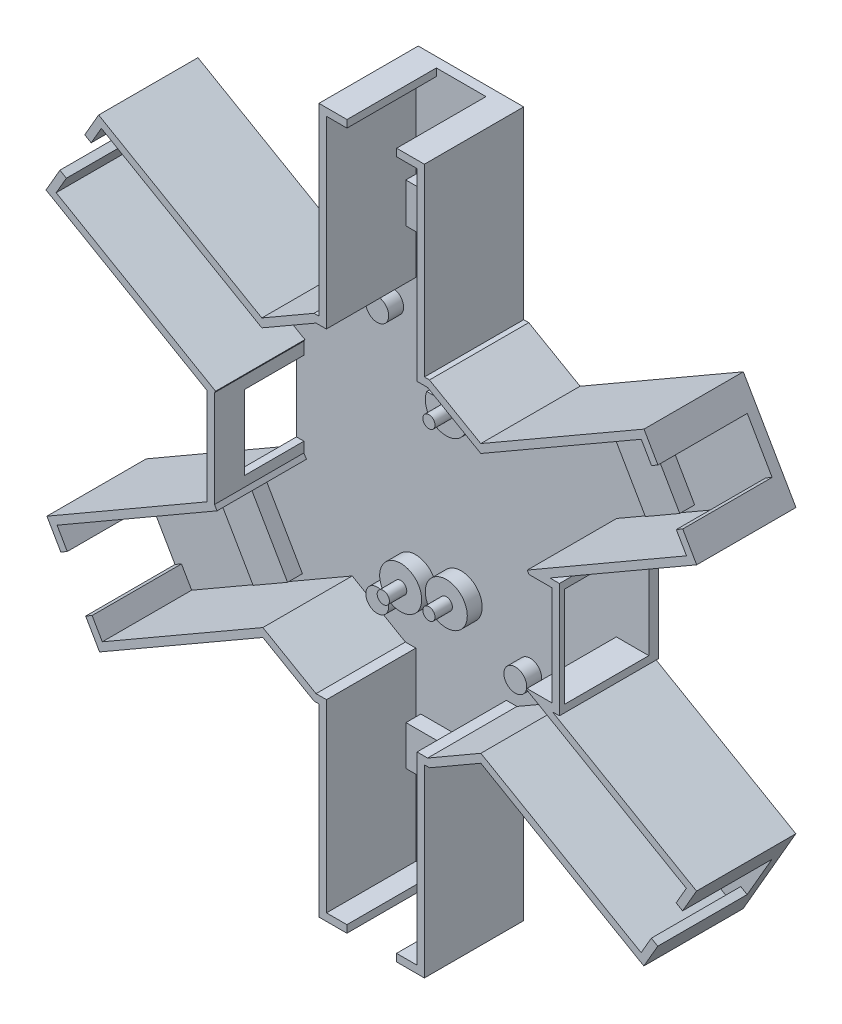
SolidWorks part; units mm, degrees
ref_plane "Ebene vorne" through (0, 0, 0) normal (0, 0, 1) x (1, 0, 0)
ref_plane "Ebene oben" through (0, 0, 0) normal (0, 1, 0) x (1, 0, 0)
ref_plane "Ebene rechts" through (0, 0, 0) normal (1, 0, 0) x (0, 0, -1)
sketch "Skizze1" plane through (0, 0, 0) normal (0, 0, 1) x (1, 0, 0)
  line L0 (-22.15, 25.11) -> (-11.02, 31.53) construction
  line L1 (-11.02, 31.53) -> (-8.35, 31.53) construction
  line L2 (-8.35, 31.53) -> (-8.35, 68.65) construction
  line L3 (-8.35, 68.65) -> (8.29, 68.65) construction
  line L4 (8.29, 68.65) -> (8.29, 31.53) construction
  line L5 (8.29, 31.53) -> (11, 31.53) construction
  line L6 (11, 31.53) -> (21.95, 25.25) construction
  line L7 (21.95, 25.25) -> (53.98, 43.72) construction
  line L8 (53.98, 43.72) -> (62.29, 29.33) construction
  line L9 (-62.48, 29.19) -> (-54.18, 43.59) construction
  line L10 (-54.18, 43.59) -> (-22.15, 25.11) construction
  line L11 (-30.38, 10.62) -> (-62.48, 29.19) construction
  line L12 (-30.88, 9.75) -> (-30.38, 10.62) construction
  line L13 (-30.88, -9.32) -> (-30.88, 9.75) construction
  line L14 (-30.05, -10.67) -> (-30.88, -9.32) construction
  line L15 (-62.3, -29.3) -> (-30.05, -10.67) construction
  line L16 (-53.99, -43.7) -> (-62.3, -29.3) construction
  line L17 (-21.73, -25.09) -> (-53.99, -43.7) construction
  line L18 (-21.52, -25.46) -> (-21.73, -25.09) construction
  line L19 (-11.02, -31.51) -> (-21.52, -25.46) construction
  line L20 (-8.33, -31.51) -> (-11.02, -31.51) construction
  line L21 (-8.33, -68.7) -> (-8.33, -31.51) construction
  line L22 (8.29, -68.7) -> (-8.33, -68.7) construction
  line L23 (8.31, -31.51) -> (8.29, -68.7) construction
  line L24 (11.02, -31.51) -> (8.31, -31.51) construction
  line L25 (21.5, -25.46) -> (11.02, -31.51) construction
  line L26 (21.73, -25.06) -> (21.5, -25.46) construction
  line L27 (53.95, -43.66) -> (21.73, -25.06) construction
  line L28 (62.26, -29.27) -> (53.95, -43.66) construction
  line L29 (30.04, -10.67) -> (62.26, -29.27) construction
  line L30 (30.79, -9.37) -> (30.04, -10.67) construction
  line L31 (35.49, -9.37) -> (30.79, -9.37) construction
  line L32 (35.49, 9.12) -> (35.49, -9.37) construction
  line L33 (31.19, 9.12) -> (35.49, 9.12) construction
  line L34 (30.22, 10.81) -> (31.19, 9.12) construction
  line L35 (62.29, 29.33) -> (30.22, 10.81) construction
  line L36 (-22.15, 25.11) -> (-11.02, 31.53) construction
  line L37 (-11.02, 31.53) -> (-8.35, 31.53) construction
  line L38 (-8.35, 31.53) -> (-8.35, 68.65) construction
  line L39 (-8.35, 68.65) -> (8.29, 68.65) construction
  line L40 (8.29, 68.65) -> (8.29, 31.53) construction
  line L41 (8.29, 31.53) -> (11, 31.53) construction
  line L42 (11, 31.53) -> (21.95, 25.25) construction
  line L43 (21.95, 25.25) -> (53.98, 43.72) construction
  line L44 (53.98, 43.72) -> (62.29, 29.33) construction
  line L45 (-62.48, 29.19) -> (-54.18, 43.59) construction
  line L46 (-54.18, 43.59) -> (-22.15, 25.11) construction
  line L47 (-30.38, 10.62) -> (-62.48, 29.19) construction
  line L48 (-30.88, 9.75) -> (-30.38, 10.62) construction
  line L49 (-30.88, -9.32) -> (-30.88, 9.75) construction
  line L50 (-30.05, -10.67) -> (-30.88, -9.32) construction
  line L51 (-62.3, -29.3) -> (-30.05, -10.67) construction
  line L52 (-53.99, -43.7) -> (-62.3, -29.3) construction
  line L53 (-21.73, -25.09) -> (-53.99, -43.7) construction
  line L54 (-21.52, -25.46) -> (-21.73, -25.09) construction
  line L55 (-11.02, -31.51) -> (-21.52, -25.46) construction
  line L56 (-8.33, -31.51) -> (-11.02, -31.51) construction
  line L57 (-8.33, -68.7) -> (-8.33, -31.51) construction
  line L58 (8.29, -68.7) -> (-8.33, -68.7) construction
  line L59 (8.31, -31.51) -> (8.29, -68.7) construction
  line L60 (11.02, -31.51) -> (8.31, -31.51) construction
  line L61 (21.5, -25.46) -> (11.02, -31.51) construction
  line L62 (21.73, -25.06) -> (21.5, -25.46) construction
  line L63 (53.95, -43.66) -> (21.73, -25.06) construction
  line L64 (62.26, -29.27) -> (53.95, -43.66) construction
  line L65 (30.04, -10.67) -> (62.26, -29.27) construction
  line L66 (30.79, -9.37) -> (30.04, -10.67) construction
  line L67 (35.49, -9.37) -> (30.79, -9.37) construction
  line L68 (35.49, 9.12) -> (35.49, -9.37) construction
  line L69 (31.19, 9.12) -> (35.49, 9.12) construction
  line L70 (30.22, 10.81) -> (31.19, 9.12) construction
  line L71 (62.29, 29.33) -> (30.22, 10.81) construction
  line L72 (-22.15, 26.0336) -> (-11.2342, 32.33)
  line L73 (-11.2342, 32.33) -> (-9.15, 32.33)
  line L74 (-9.15, 32.33) -> (-9.15, 69.45)
  line L75 (-9.15, 69.45) -> (9.09, 69.45)
  line L76 (9.09, 69.45) -> (9.09, 32.33)
  line L77 (9.09, 32.33) -> (11.2131, 32.33)
  line L78 (11.2131, 32.33) -> (21.9489, 26.1729)
  line L79 (21.9489, 26.1729) -> (54.273, 44.8124)
  line L80 (54.273, 44.8124) -> (63.3828, 29.0373)
  line L81 (63.3828, 29.0373) -> (31.311, 10.5162)
  line L82 (31.311, 10.5162) -> (31.6532, 9.92)
  line L83 (31.6532, 9.92) -> (36.29, 9.92)
  line L84 (36.29, 9.92) -> (36.29, -10.17)
  line L85 (36.29, -10.17) -> (31.2521, -10.17)
  line L86 (31.2521, -10.17) -> (31.1326, -10.377)
  line L87 (31.1326, -10.377) -> (63.3529, -28.9772)
  line L88 (63.3529, -28.9772) -> (54.2428, -44.7527)
  line L89 (54.2428, -44.7527) -> (21.9615, -26.1173)
  line L90 (21.9615, -26.1173) -> (21.9615, -26.1173)
  line L91 (21.9615, -26.1173) -> (11.2343, -32.31)
  line L92 (11.2343, -32.31) -> (9.1096, -32.31)
  line L93 (9.1096, -32.31) -> (9.0896, -69.5)
  line L94 (9.0896, -69.5) -> (-9.13, -69.5)
  line L95 (-9.13, -69.5) -> (-9.13, -32.31)
  line L96 (-9.13, -32.31) -> (-11.234, -32.31)
  line L97 (-11.234, -32.31) -> (-21.9457, -26.138)
  line L98 (-21.9457, -26.138) -> (-21.9457, -26.138)
  line L99 (-21.9457, -26.138) -> (-54.2831, -44.7927)
  line L100 (-54.2831, -44.7927) -> (-63.3926, -29.0073)
  line L101 (-63.3926, -29.0073) -> (-31.1621, -10.3886)
  line L102 (-31.1621, -10.3886) -> (-31.68, -9.5463)
  line L103 (-31.68, -9.5463) -> (-31.68, 9.9635)
  line L104 (-31.68, 9.9635) -> (-31.4711, 10.327)
  line L105 (-31.4711, 10.327) -> (-63.572, 28.8975)
  line L106 (-63.572, 28.8975) -> (-54.4734, 44.6829)
  line L107 (-54.4734, 44.6829) -> (-22.15, 26.0336)
  line L108 (-22.1499, 27.7653) -> (-11.6358, 33.83)
  line L109 (-11.6358, 33.83) -> (-10.65, 33.83)
  line L110 (-10.65, 33.83) -> (-10.65, 70.95)
  line L111 (-10.65, 70.95) -> (10.59, 70.95)
  line L112 (10.59, 70.95) -> (10.59, 33.83)
  line L113 (10.59, 33.83) -> (11.6127, 33.83)
  line L114 (11.6127, 33.83) -> (21.9469, 27.9032)
  line L115 (21.9469, 27.9032) -> (54.8223, 46.8607)
  line L116 (54.8223, 46.8607) -> (65.4319, 28.4885)
  line L117 (65.4319, 28.4885) -> (35.8755, 11.42)
  line L118 (35.8755, 11.42) -> (35.8755, 11.42)
  line L119 (35.8755, 11.42) -> (37.79, 11.42)
  line L120 (37.79, 11.42) -> (37.79, -11.67)
  line L121 (37.79, -11.67) -> (36.3727, -11.67)
  line L122 (36.3727, -11.67) -> (36.3727, -11.67)
  line L123 (36.3727, -11.67) -> (65.4021, -28.4282)
  line L124 (65.4021, -28.4282) -> (54.7917, -46.8016)
  line L125 (54.7917, -46.8016) -> (21.9615, -27.8493)
  line L126 (21.9615, -27.8493) -> (21.9615, -27.8493)
  line L127 (21.9615, -27.8493) -> (11.6362, -33.81)
  line L128 (11.6362, -33.81) -> (10.6088, -33.81)
  line L129 (10.6088, -33.81) -> (10.5888, -71)
  line L130 (10.5888, -71) -> (-10.63, -71)
  line L131 (-10.63, -71) -> (-10.63, -33.81)
  line L132 (-10.63, -33.81) -> (-11.6352, -33.81)
  line L133 (-11.6352, -33.81) -> (-21.9453, -27.8694)
  line L134 (-21.9453, -27.8694) -> (-21.9453, -27.8694)
  line L135 (-21.9453, -27.8694) -> (-54.8327, -46.8414)
  line L136 (-54.8327, -46.8414) -> (-65.4412, -28.4584)
  line L137 (-65.4412, -28.4584) -> (-33.18, -9.8219)
  line L138 (-33.18, -9.8219) -> (-33.18, -9.8219)
  line L139 (-33.18, -9.8219) -> (-33.18, 9.5827)
  line L140 (-33.18, 9.5827) -> (-33.18, 9.5827)
  line L141 (-33.18, 9.5827) -> (-65.6194, 28.349)
  line L142 (-65.6194, 28.349) -> (-55.0236, 46.7321)
  line L143 (-55.0236, 46.7321) -> (-22.1499, 27.7653)
  dimension "D1" = 0.8
  dimension "D2" = 1.5
extrude "Aufsatz-Linear austragen1" add sketch "Skizze1" along normal blind 18
sketch "Skizze3" plane through (0, 0, 0) normal (0, 0, -1) x (-1, 0, 0)
  line L31 (55.0236, 46.7321) -> (22.1499, 27.7653)
  line L32 (22.1499, 27.7653) -> (11.6358, 33.83)
  line L33 (11.6358, 33.83) -> (10.65, 33.83)
  line L34 (10.65, 33.83) -> (10.65, 70.95)
  line L35 (10.65, 70.95) -> (-10.59, 70.95)
  line L36 (-10.59, 70.95) -> (-10.59, 33.83)
  line L37 (-10.59, 33.83) -> (-11.6127, 33.83)
  line L38 (-11.6127, 33.83) -> (-21.9469, 27.9032)
  line L39 (-21.9469, 27.9032) -> (-54.8223, 46.8607)
  line L40 (-54.8223, 46.8607) -> (-65.4319, 28.4885)
  line L41 (-65.4319, 28.4885) -> (-35.8755, 11.42)
  line L42 (-35.8755, 11.42) -> (-37.79, 11.42)
  line L43 (-37.79, 11.42) -> (-37.79, -11.67)
  line L44 (-37.79, -11.67) -> (-36.3727, -11.67)
  line L45 (-36.3727, -11.67) -> (-65.4021, -28.4282)
  line L46 (-65.4021, -28.4282) -> (-54.7917, -46.8016)
  line L47 (-54.7917, -46.8016) -> (-21.9615, -27.8493)
  line L48 (-21.9615, -27.8493) -> (-11.6362, -33.81)
  line L49 (-11.6362, -33.81) -> (-10.6088, -33.81)
  line L50 (-10.6088, -33.81) -> (-10.5888, -71)
  line L51 (-10.5888, -71) -> (10.63, -71)
  line L52 (10.63, -71) -> (10.63, -33.81)
  line L53 (10.63, -33.81) -> (11.6352, -33.81)
  line L54 (11.6352, -33.81) -> (21.9453, -27.8694)
  line L55 (21.9453, -27.8694) -> (54.8327, -46.8414)
  line L56 (54.8327, -46.8414) -> (65.4412, -28.4584)
  line L57 (65.4412, -28.4584) -> (33.18, -9.8219)
  line L59 (33.18, -9.8219) -> (33.18, 9.5827)
  line L60 (33.18, 9.5827) -> (65.6194, 28.349)
  line L61 (65.6194, 28.349) -> (55.0236, 46.7321)
  line L62 (55.0236, 46.7321) -> (22.1499, 27.7653)
  line L63 (22.1499, 27.7653) -> (11.6358, 33.83)
  line L64 (11.6358, 33.83) -> (10.65, 33.83)
  line L65 (10.65, 33.83) -> (10.65, 70.95)
  line L66 (10.65, 70.95) -> (-10.59, 70.95)
  line L67 (-10.59, 70.95) -> (-10.59, 33.83)
  line L68 (-10.59, 33.83) -> (-11.6127, 33.83)
  line L69 (-11.6127, 33.83) -> (-21.9469, 27.9032)
  line L70 (-21.9469, 27.9032) -> (-54.8223, 46.8607)
  line L71 (-54.8223, 46.8607) -> (-65.4319, 28.4885)
  line L72 (-65.4319, 28.4885) -> (-35.8755, 11.42)
  line L73 (-35.8755, 11.42) -> (-37.79, 11.42)
  line L74 (-37.79, 11.42) -> (-37.79, -11.67)
  line L75 (-37.79, -11.67) -> (-36.3727, -11.67)
  line L76 (-36.3727, -11.67) -> (-65.4021, -28.4282)
  line L77 (-65.4021, -28.4282) -> (-54.7917, -46.8016)
  line L78 (-54.7917, -46.8016) -> (-21.9615, -27.8493)
  line L79 (-21.9615, -27.8493) -> (-11.6362, -33.81)
  line L80 (-11.6362, -33.81) -> (-10.6088, -33.81)
  line L81 (-10.6088, -33.81) -> (-10.5888, -71)
  line L82 (-10.5888, -71) -> (10.63, -71)
  line L83 (10.63, -71) -> (10.63, -33.81)
  line L84 (10.63, -33.81) -> (11.6352, -33.81)
  line L85 (11.6352, -33.81) -> (21.9453, -27.8694)
  line L86 (21.9453, -27.8694) -> (54.8327, -46.8414)
  line L87 (54.8327, -46.8414) -> (65.4412, -28.4584)
  line L88 (65.4412, -28.4584) -> (33.18, -9.8219)
  line L90 (33.18, -9.8219) -> (33.18, 9.5827)
  line L91 (33.18, 9.5827) -> (65.6194, 28.349)
  line L92 (65.6194, 28.349) -> (55.0236, 46.7321)
  dimension "D1" = 0
extrude "Aufsatz-Linear austragen2" add sketch "Skizze3" along normal blind 2
sketch "Skizze4" plane through (36.29, 0, 0) normal (-1, 0, 0) x (0, 0, 1)
  line L0 (17.0038, 9.92) -> (17.0038, -10.17)
  line L1 (0.8513, 9.92) -> (0, 9.92)
  line L2 (17.0038, -10.17) -> (0.8513, -10.17)
  line L3 (17.0038, 9.92) -> (0.8513, 9.92)
  line L4 (0, 9.92) -> (0, -10.17)
  line L5 (0, -10.17) -> (18, -10.17)
  line L6 (18, -10.17) -> (18, 9.92)
  line L7 (18, 9.92) -> (0, 9.92)
  line L8 (0, 9.92) -> (0, -10.17) construction
  line L9 (0, -10.17) -> (18, -10.17) construction
  line L10 (18, -10.17) -> (18, 9.92) construction
  line L11 (18, 9.92) -> (0, 9.92) construction
  line L12 (0, 9.92) -> (0, -10.17)
  line L13 (0, -10.17) -> (0.8513, -10.17)
  dimension "D1" = 0
extrude "Schnitt-Linear austragen1" cut sketch "Skizze4" against normal up to next
sketch "Skizze5" plane through (-31.68, 0, 0) normal (1, 0, 0) x (0, 0, -1)
  line L0 (-12, -7.5) -> (-12, 7.5)
  line L1 (-12, -7.5) -> (0, -7.5)
  line L2 (-12, 7.5) -> (0, 7.5)
  line L3 (0, -7.5) -> (0, 7.5)
  line L4 (-12, -7.5) -> (0, 7.5) construction
  line L5 (-12, 7.5) -> (0, -7.5) construction
  line L6 (0, 9.9635) -> (0, -9.5463) construction
  point P1 (-6, 0)
  dimension "D1" = 15
  dimension "D2" = 12
  dimension "D3" = 0
extrude "Schnitt-Linear austragen2" cut sketch "Skizze5" against normal up to next
sketch "Skizze6" plane through (0, -71, 0) normal (0, -1, 0) x (1, 0, 0)
  line L0 (-9.13, 0) -> (9.0896, 0) construction
  line L1 (5, 10) -> (-5, 10)
  line L2 (5, 10) -> (5, 0)
  line L3 (5, 0) -> (-5, 0)
  line L4 (-5, 10) -> (-5, 0)
  line L5 (5, 10) -> (-5, 0) construction
  line L6 (5, 0) -> (-5, 10) construction
  line L7 (-9.13, 0) -> (9.0896, 0) construction
  point P0 (0, 5)
  dimension "D1" = 10
  dimension "D2" = 10
sketch "Skizze7" plane through (0, 0, 0) normal (0, 0, 1) x (1, 0, 0)
  circle A0 centre (-9.19, -20.27) radius 1.35 construction
  circle A1 centre (0, -18.5) radius 1.35 construction
  circle A2 centre (0, 15) radius 1.35 construction
  circle A3 centre (-9.19, -20.27) radius 4.35
  circle A4 centre (0, -18.5) radius 4.35
  circle A5 centre (0, 15) radius 4.35
  circle A6 centre (0, 15) radius 1.23
  circle A7 centre (0, -18.5) radius 1.23
  circle A8 centre (-9.19, -20.27) radius 1.23
  point P0 (-9.19, -21.62)
  point P1 (-7.84, -20.27)
  point P2 (-9.19, -18.92)
  point P3 (0, -17.15)
  point P5 (-1.35, -18.5)
  point P6 (0, -19.85)
  point P7 (-1.35, 15)
  point P8 (0, 16.35)
  point P13 (1.35, 15)
  dimension "D1" = 3
  dimension "D2" = 0.12
  dimension "D3" = 0.12
  dimension "D4" = 0.12
extrude "Aufsatz-Linear austragen3" add sketch "Skizze7" along normal blind 6.5 contours A6 | A7 | A8
sketch "Skizze8" plane through (0, 0, 0) normal (0, 0, 1) x (1, 0, 0)
  line L0 (3.9365, 16.5483) -> (-3.9365, 16.5483)
  circle A0 centre (-9.19, -20.27) radius 1.23 construction
  circle A1 centre (-9.19, -20.27) radius 1.23 construction
  circle A2 centre (0, -18.5) radius 1.23 construction
  circle A3 centre (0, -18.5) radius 1.23 construction
  circle A4 centre (0, 15) radius 1.23 construction
  circle A5 centre (0, 15) radius 1.23 construction
  circle A6 centre (-9.19, -20.27) radius 4.23
  circle A7 centre (0, -18.5) radius 4.23
  arc A8 (-3.9365, 16.5483) -> (3.9365, 16.5483) centre (0, 15) ccw
  circle A9 centre (0, 15) radius 4.23 construction
  circle A10 centre (13.9, 25.8971) radius 2.3
  circle A11 centre (-13.9, 25.8971) radius 2.3
  circle A12 centre (13.9, -24.8616) radius 2.3
  circle A13 centre (-13.9, -24.8616) radius 2.3
  dimension "D2" = 4.6
  dimension "D3" = 4.6
  dimension "D4" = 4.6
  dimension "D5" = 4.6
  dimension "D6" = 13.9
  dimension "D7" = 13.9
  dimension "D1" = 3
extrude "Aufsatz-Linear austragen4" add sketch "Skizze8" along normal blind 3
sketch "Skizze9" plane through (0, 0, 0) normal (0, 0, 1) x (1, 0, 0)
  line L0 (-9.13, -42.31) -> (-9.13, -52.31) construction
  line L1 (-9.13, -42.31) -> (9.0954, -42.31) construction
  line L2 (-9.13, -52.31) -> (9.0954, -52.31) construction
  line L3 (9.0954, -42.31) -> (9.0954, -52.31) construction
  line L4 (30.622, -31.1169) -> (39.2825, -36.1164) construction
  line L5 (30.622, -31.1169) -> (39.7347, -15.3313) construction
  line L6 (39.2825, -36.1164) -> (48.3952, -20.3309) construction
  line L7 (39.7347, -15.3313) -> (48.3952, -20.3309) construction
  line L8 (39.7303, 15.3783) -> (48.3901, 20.3792) construction
  line L9 (39.7303, 15.3783) -> (30.62, 31.1541) construction
  line L10 (48.3901, 20.3792) -> (39.2797, 36.155) construction
  line L11 (30.62, 31.1541) -> (39.2797, 36.155) construction
  line L12 (9.09, 42.33) -> (9.09, 52.33) construction
  line L13 (9.09, 42.33) -> (-9.1623, 42.33) construction
  line L14 (9.09, 52.33) -> (-9.1623, 52.33) construction
  line L15 (-9.1623, 42.33) -> (-9.1623, 52.33) construction
  line L16 (-39.4734, 36.0285) -> (-30.8117, 31.031) construction
  line L17 (-39.4734, 36.0285) -> (-48.6218, 20.1723) construction
  line L18 (-30.8117, 31.031) -> (-39.9601, 15.1748) construction
  line L19 (-48.6218, 20.1723) -> (-39.9601, 15.1748) construction
  line L20 (-48.3915, -20.3415) -> (-39.7324, -15.3394) construction
  line L21 (-48.3915, -20.3415) -> (-39.2717, -36.1285) construction
  line L22 (-39.7324, -15.3394) -> (-30.6127, -31.1264) construction
  line L23 (-39.2717, -36.1285) -> (-30.6127, -31.1264) construction
  line L24 (-39.107, 34.6626) -> (-47.2559, 20.5387)
  line L25 (-47.2559, 20.5387) -> (-40.3265, 16.5407)
  line L26 (-32.1776, 30.6646) -> (-40.3265, 16.5407)
  line L27 (-39.107, 34.6626) -> (-32.1776, 30.6646)
  line L28 (-8.1623, 43.33) -> (-8.1623, 51.33)
  line L29 (8.09, 51.33) -> (-8.1623, 51.33)
  line L30 (8.09, 43.33) -> (8.09, 51.33)
  line L31 (8.09, 43.33) -> (-8.1623, 43.33)
  line L32 (40.0962, 16.7443) -> (31.9861, 30.7882)
  line L33 (31.9861, 30.7882) -> (38.9139, 34.7889)
  line L34 (47.024, 20.745) -> (38.9139, 34.7889)
  line L35 (40.0962, 16.7443) -> (47.024, 20.745)
  line L36 (40.1008, -16.6973) -> (47.0292, -20.6969)
  line L37 (38.9164, -34.7504) -> (47.0292, -20.6969)
  line L38 (31.988, -30.7508) -> (38.9164, -34.7504)
  line L39 (31.988, -30.7508) -> (40.1008, -16.6973)
  line L40 (8.0954, -43.31) -> (8.0954, -51.31)
  line L41 (-8.13, -51.31) -> (8.0954, -51.31)
  line L42 (-8.13, -43.31) -> (-8.13, -51.31)
  line L43 (-8.13, -43.31) -> (8.0954, -43.31)
  line L44 (-38.906, -34.7624) -> (-31.9788, -30.7607)
  line L45 (-40.0981, -16.7055) -> (-31.9788, -30.7607)
  line L46 (-47.0253, -20.7072) -> (-40.0981, -16.7055)
  line L47 (-47.0253, -20.7072) -> (-38.906, -34.7624)
  line L50 (-11.2342, 32.33) -> (-22.15, 26.0336)
  line L51 (-22.15, 26.0336) -> (-54.4734, 44.6829)
  line L52 (-54.4734, 44.6829) -> (-63.572, 28.8975)
  line L53 (-63.572, 28.8975) -> (-31.4711, 10.327)
  line L54 (-31.4711, 10.327) -> (-31.68, 9.9635)
  line L55 (-31.68, 9.9635) -> (-31.68, 7.5)
  line L56 (-31.68, 7.5) -> (-33.18, 7.5)
  line L57 (-33.18, 7.5) -> (-33.18, -7.5)
  line L58 (-33.18, -7.5) -> (-31.68, -7.5)
  line L59 (-31.68, -7.5) -> (-31.68, -9.5463)
  line L60 (-31.68, -9.5463) -> (-31.1621, -10.3886)
  line L61 (-31.1621, -10.3886) -> (-63.3926, -29.0073)
  line L62 (-63.3926, -29.0073) -> (-54.2831, -44.7927)
  line L63 (-54.2831, -44.7927) -> (-21.9457, -26.138)
  line L64 (-21.9457, -26.138) -> (-11.234, -32.31)
  line L65 (-11.234, -32.31) -> (-9.13, -32.31)
  line L66 (-9.13, -32.31) -> (-9.13, -69.5)
  line L67 (-9.13, -69.5) -> (9.0896, -69.5)
  line L68 (9.0896, -69.5) -> (9.1096, -32.31)
  line L69 (9.1096, -32.31) -> (11.2343, -32.31)
  line L70 (11.2343, -32.31) -> (21.9615, -26.1173)
  line L71 (21.9615, -26.1173) -> (54.2428, -44.7527)
  line L72 (54.2428, -44.7527) -> (63.3529, -28.9772)
  line L73 (63.3529, -28.9772) -> (31.1326, -10.377)
  line L74 (31.1326, -10.377) -> (31.2521, -10.17)
  line L75 (31.2521, -10.17) -> (37.79, -10.17)
  line L76 (37.79, -10.17) -> (37.79, 9.92)
  line L77 (37.79, 9.92) -> (31.6532, 9.92)
  line L78 (31.6532, 9.92) -> (31.311, 10.5162)
  line L79 (31.311, 10.5162) -> (63.3828, 29.0373)
  line L80 (63.3828, 29.0373) -> (54.273, 44.8124)
  line L81 (54.273, 44.8124) -> (21.9489, 26.1729)
  line L82 (21.9489, 26.1729) -> (11.2131, 32.33)
  line L83 (11.2131, 32.33) -> (9.09, 32.33)
  line L84 (9.09, 32.33) -> (9.09, 69.45)
  line L85 (9.09, 69.45) -> (-9.15, 69.45)
  line L86 (-9.15, 69.45) -> (-9.15, 32.33)
  line L87 (-9.15, 32.33) -> (-11.2342, 32.33)
  line L88 (-11.2342, 32.33) -> (-22.15, 26.0336) construction
  line L89 (-22.15, 26.0336) -> (-54.4734, 44.6829) construction
  line L90 (-54.4734, 44.6829) -> (-63.572, 28.8975) construction
  line L91 (-63.572, 28.8975) -> (-31.4711, 10.327) construction
  line L92 (-31.4711, 10.327) -> (-31.68, 9.9635) construction
  line L93 (-31.68, 9.9635) -> (-31.68, 7.5) construction
  line L94 (-31.68, 7.5) -> (-33.18, 7.5) construction
  line L95 (-33.18, 7.5) -> (-33.18, -7.5) construction
  line L96 (-33.18, -7.5) -> (-31.68, -7.5) construction
  line L97 (-31.68, -7.5) -> (-31.68, -9.5463) construction
  line L98 (-31.68, -9.5463) -> (-31.1621, -10.3886) construction
  line L99 (-31.1621, -10.3886) -> (-63.3926, -29.0073) construction
  line L100 (-63.3926, -29.0073) -> (-54.2831, -44.7927) construction
  line L101 (-54.2831, -44.7927) -> (-21.9457, -26.138) construction
  line L102 (-21.9457, -26.138) -> (-11.234, -32.31) construction
  line L103 (-11.234, -32.31) -> (-9.13, -32.31) construction
  line L104 (-9.13, -32.31) -> (-9.13, -69.5) construction
  line L105 (-9.13, -69.5) -> (9.0896, -69.5) construction
  line L106 (9.0896, -69.5) -> (9.1096, -32.31) construction
  line L107 (9.1096, -32.31) -> (11.2343, -32.31) construction
  line L108 (11.2343, -32.31) -> (21.9615, -26.1173) construction
  line L109 (21.9615, -26.1173) -> (54.2428, -44.7527) construction
  line L110 (54.2428, -44.7527) -> (63.3529, -28.9772) construction
  line L111 (63.3529, -28.9772) -> (31.1326, -10.377) construction
  line L112 (31.1326, -10.377) -> (31.2521, -10.17) construction
  line L113 (31.2521, -10.17) -> (37.79, -10.17) construction
  line L114 (37.79, -10.17) -> (37.79, 9.92) construction
  line L115 (37.79, 9.92) -> (31.6532, 9.92) construction
  line L116 (31.6532, 9.92) -> (31.311, 10.5162) construction
  line L117 (31.311, 10.5162) -> (63.3828, 29.0373) construction
  line L118 (63.3828, 29.0373) -> (54.273, 44.8124) construction
  line L119 (54.273, 44.8124) -> (21.9489, 26.1729) construction
  line L120 (21.9489, 26.1729) -> (11.2131, 32.33) construction
  line L121 (11.2131, 32.33) -> (9.09, 32.33) construction
  line L122 (9.09, 32.33) -> (9.09, 69.45) construction
  line L123 (9.09, 69.45) -> (-9.15, 69.45) construction
  line L124 (-9.15, 69.45) -> (-9.15, 32.33) construction
  line L125 (-9.15, 32.33) -> (-11.2342, 32.33) construction
  dimension "D1" = 0
  dimension "D2" = 10
  dimension "D3" = 10
  dimension "D4" = 10
  dimension "D5" = 10
  dimension "D6" = 10
  dimension "D7" = 10
  dimension "D8" = 10
  dimension "D9" = 10
  dimension "D10" = 10
  dimension "D11" = 10
  dimension "D12" = 10
  dimension "D13" = 10
  dimension "D14" = 1
extrude "Aufsatz-Linear austragen7" add sketch "Skizze9" along normal blind 3
sketch "Skizze11" plane through (0, 69.45, 0) normal (0, -1, 0) x (1, 0, 0)
  line L1 (-5, 0) -> (5, 0)
  line L2 (-5, 0) -> (-5, 10)
  line L3 (-5, 10) -> (5, 10)
  line L4 (-9.15, 0) -> (9.09, 0)
  line L5 (9.09, 0) -> (9.09, 18)
  line L6 (9.09, 18) -> (-9.15, 18)
  line L7 (-9.15, 18) -> (-9.15, 0)
  line L8 (-9.15, 0) -> (9.09, 0) construction
  line L9 (9.09, 0) -> (9.09, 18) construction
  line L10 (9.09, 18) -> (-9.15, 18) construction
  line L11 (-9.15, 18) -> (-9.15, 0) construction
  line L12 (5, 0) -> (5, 10)
  dimension "D2" = 5
  dimension "D3" = 10
  dimension "D4" = 10
  dimension "D1" = 0
extrude "Schnitt-Linear austragen3" cut sketch "Skizze11" against normal up to next
sketch "Skizze12" plane through (-60.2212, 34.7108, 0) normal (0.8664, -0.4994, 0) x (0, 0, -1)
  line L4 (0, -6.7099) -> (0, 11.51)
  line L5 (0, 11.51) -> (-18, 11.51)
  line L6 (-18, 11.51) -> (-18, -6.7099)
  line L7 (-18, -6.7099) -> (0, -6.7099)
  line L8 (0, -6.7099) -> (0, 11.51) construction
  line L9 (0, 11.51) -> (-18, 11.51) construction
  line L10 (-18, 11.51) -> (-18, -6.7099) construction
  line L11 (-18, -6.7099) -> (0, -6.7099) construction
  dimension "D1" = 0
ref_axis "Achse1" through (0, 0, -3) along (0, 0, 1)
sketch "Skizze13" plane through (60.1066, 34.7106, 0) normal (-0.866, -0.5001, 0) x (0, 0, 1)
  line L0 (0, -6.5514) -> (0, 11.6652) construction
  line L1 (0, -6.5514) -> (0, 11.6652) construction
  line L2 (0, 7.5569) -> (0, -2.4431)
  line L3 (0, 7.5569) -> (10, 7.5569)
  line L4 (0, -2.4431) -> (10, -2.4431)
  line L5 (10, 7.5569) -> (10, -2.4431)
  point P2 (0, 2.5569)
  point P5 (0, 2.5569)
  dimension "D1" = 10
  dimension "D2" = 10
extrude "Schnitt-Linear austragen4" cut sketch "Skizze13" against normal up to next
sketch "Skizze14" plane through (60.0581, -34.6826, 0) normal (-0.866, 0.5001, 0) x (0, 0, 1)
  line L0 (0, -11.6286) -> (0, 6.5885) construction
  line L1 (0, -11.6286) -> (0, 6.5885) construction
  line L2 (0, 2.4799) -> (0, -7.5201)
  line L3 (0, 2.4799) -> (10, 2.4799)
  line L4 (0, -7.5201) -> (10, -7.5201)
  line L5 (10, 2.4799) -> (10, -7.5201)
  point P2 (0, -2.5201)
  point P3 (0, -2.5201)
  dimension "D1" = 10
  dimension "D2" = 10
extrude "Schnitt-Linear austragen5" cut sketch "Skizze14" against normal up to next
sketch "Skizze15" plane through (0, -69.5, 0) normal (0, 1, 0) x (1, 0, 0)
  line L0 (-9.13, 0) -> (9.0896, 0) construction
  line L1 (-9.13, 0) -> (9.0896, 0) construction
  line L2 (-5.0202, 0) -> (4.9798, 0)
  line L3 (-5.0202, 0) -> (-5.0202, -10)
  line L4 (4.9798, 0) -> (4.9798, -10)
  line L5 (-5.0202, -10) -> (4.9798, -10)
  point P2 (-0.0202, 0)
  point P3 (-0.0202, 0)
  dimension "D1" = 10
  dimension "D2" = 10
extrude "Schnitt-Linear austragen6" cut sketch "Skizze15" against normal up to next
sketch "Skizze16" plane through (-60.113, -34.6902, 0) normal (0.8661, 0.4998, 0) x (0, 0, -1)
  line L0 (0, 6.5614) -> (0, -11.6639) construction
  line L1 (0, 6.5614) -> (0, -11.6639) construction
  line L2 (0, 2.4487) -> (0, -7.5513)
  line L3 (0, 2.4487) -> (-10, 2.4487)
  line L4 (0, -7.5513) -> (-10, -7.5513)
  line L5 (-10, 2.4487) -> (-10, -7.5513)
  point P2 (0, -2.5513)
  point P3 (0, -2.5513)
  dimension "D1" = 10
  dimension "D2" = 10
extrude "Schnitt-Linear austragen7" cut sketch "Skizze16" against normal up to next
sketch "Skizze17" plane through (-60.2212, 34.7108, 0) normal (0.8664, -0.4994, 0) x (0, 0, -1)
  line L0 (0, 11.51) -> (0, -6.7099) construction
  line L1 (0, 11.51) -> (0, -6.7099) construction
  line L2 (0, 7.4) -> (0, -2.6)
  line L3 (0, 7.4) -> (-10, 7.4)
  line L4 (0, -2.6) -> (-10, -2.6)
  line L5 (-10, 7.4) -> (-10, -2.6)
  point P2 (0, 2.4)
  point P3 (0, 2.4)
  dimension "D1" = 10
  dimension "D2" = 10
extrude "Schnitt-Linear austragen8" cut sketch "Skizze17" against normal up to next
sketch "Skizze18" plane through (0, 0, 10) normal (0, 0, -1) x (-1, 0, 0)
  line L4 (-62.5972, -33.2852) -> (-57.5964, -41.945)
  line L5 (-57.5964, -41.945) -> (-56.2974, -41.1948)
  line L6 (-56.2974, -41.1948) -> (-61.2983, -32.5351)
  line L7 (-61.2983, -32.5351) -> (-62.5972, -33.2852)
  line L8 (-62.5972, -33.2852) -> (-57.5964, -41.945)
  line L9 (-57.5964, -41.945) -> (-56.2974, -41.1948)
  line L10 (-56.2974, -41.1948) -> (-61.2983, -32.5351)
  line L11 (-61.2983, -32.5351) -> (-62.5972, -33.2852)
  line L12 (-4.9798, -71) -> (5.0202, -71)
  line L13 (5.0202, -71) -> (5.0202, -69.5)
  line L14 (5.0202, -69.5) -> (-4.9798, -69.5)
  line L15 (-4.9798, -69.5) -> (-4.9798, -71)
  line L16 (-4.9798, -71) -> (5.0202, -71)
  line L17 (5.0202, -71) -> (5.0202, -69.5)
  line L18 (5.0202, -69.5) -> (-4.9798, -69.5)
  line L19 (-4.9798, -69.5) -> (-4.9798, -71)
  line L20 (57.6379, -41.9803) -> (62.6362, -33.3191)
  line L21 (62.6362, -33.3191) -> (61.337, -32.5693)
  line L22 (61.337, -32.5693) -> (56.3387, -41.2306)
  line L23 (56.3387, -41.2306) -> (57.6379, -41.9803)
  line L24 (57.6379, -41.9803) -> (62.6362, -33.3191)
  line L25 (62.6362, -33.3191) -> (61.337, -32.5693)
  line L26 (61.337, -32.5693) -> (56.3387, -41.2306)
  line L27 (56.3387, -41.2306) -> (57.6379, -41.9803)
  line L28 (62.8192, 33.2073) -> (57.8254, 41.8712)
  line L29 (57.8254, 41.8712) -> (56.5258, 41.1221)
  line L30 (56.5258, 41.1221) -> (61.5196, 32.4583)
  line L31 (61.5196, 32.4583) -> (62.8192, 33.2073)
  line L32 (62.8192, 33.2073) -> (57.8254, 41.8712)
  line L33 (57.8254, 41.8712) -> (56.5258, 41.1221)
  line L34 (56.5258, 41.1221) -> (61.5196, 32.4583)
  line L35 (61.5196, 32.4583) -> (62.8192, 33.2073)
  line L36 (5, 70.95) -> (-5, 70.95)
  line L37 (-5, 70.95) -> (-5, 69.45)
  line L38 (-5, 69.45) -> (5, 69.45)
  line L39 (5, 69.45) -> (5, 70.95)
  line L40 (5, 70.95) -> (-5, 70.95)
  line L41 (-5, 70.95) -> (-5, 69.45)
  line L42 (-5, 69.45) -> (5, 69.45)
  line L43 (5, 69.45) -> (5, 70.95)
  line L44 (-57.6264, 42.0049) -> (-62.6273, 33.3451)
  line L45 (-62.6273, 33.3451) -> (-61.3283, 32.595)
  line L46 (-61.3283, 32.595) -> (-56.3275, 41.2547)
  line L47 (-56.3275, 41.2547) -> (-57.6264, 42.0049)
  line L48 (-57.6264, 42.0049) -> (-62.6273, 33.3451)
  line L49 (-62.6273, 33.3451) -> (-61.3283, 32.595)
  line L50 (-61.3283, 32.595) -> (-56.3275, 41.2547)
  line L51 (-56.3275, 41.2547) -> (-57.6264, 42.0049)
  dimension "D1" = 0
  dimension "D2" = 0
  dimension "D3" = 0
  dimension "D4" = 0
  dimension "D5" = 0
  dimension "D6" = 0
extrude "Schnitt-Linear austragen9" cut sketch "Skizze18" against normal up to surface (8 mm away) up to face at (2.6869, -0.0303, 18)
